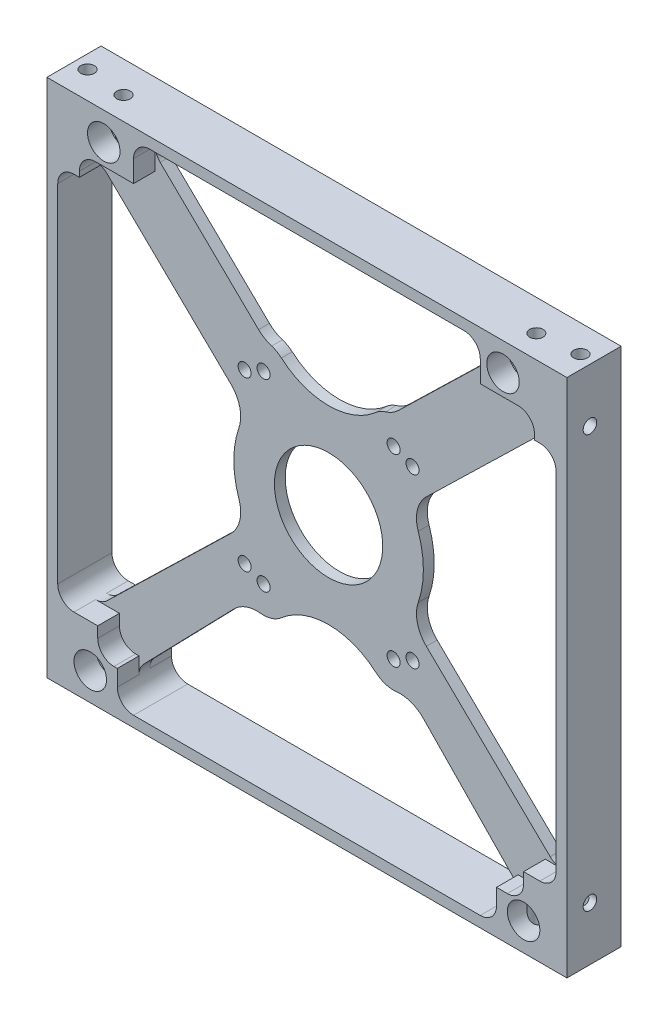
SolidWorks part; units mm, degrees
material "7075-T6 (SN)"
ref_plane "Front Plane" through (0, 0, 0) normal (0, 0, 1) x (1, 0, 0)
ref_plane "Top Plane" through (0, 0, 0) normal (0, 1, 0) x (1, 0, 0)
ref_plane "Right Plane" through (0, 0, 0) normal (1, 0, 0) x (0, 0, -1)
sketch "Sketch1" plane through (0, 0, 0) normal (0, 0, 1) x (1, 0, 0)
  line L0 (-38, 42) -> (-38, 38)
  line L1 (48, -48) -> (-48, -48)
  line L2 (48, -48) -> (48, 48)
  line L3 (48, 48) -> (-48, 48)
  line L4 (-48, -48) -> (-48, 48)
  line L5 (48, -48) -> (-48, 48) construction
  line L6 (48, 48) -> (-48, -48) construction
  line L7 (42, -42) -> (-42, -42)
  line L8 (42, -42) -> (42, 42)
  line L9 (42, 42) -> (-42, 42)
  line L10 (-42, -42) -> (-42, 42)
  line L11 (42, -42) -> (-42, 42) construction
  line L12 (42, 42) -> (-42, -42) construction
  line L13 (-38, 38) -> (-42, 38)
  line L14 (42, 38) -> (38, 38)
  line L15 (38, 38) -> (38, 42)
  line L16 (38, -42) -> (38, -38)
  line L17 (38, -38) -> (42, -38)
  line L18 (-42, -38) -> (-38, -38)
  line L19 (-38, -38) -> (-38, -42)
  point P0 (0, 0)
  point P6 (0, 0)
  point P26 (0, 0)
  dimension "D1" = 96
  dimension "D2" = 96
  dimension "D3" = 6
  dimension "D4" = 84
  dimension "D5" = 10
  dimension "D6" = 4
extrude "Boss-Extrude1" add sketch "Sketch1" along normal blind 10 contours L4 L1 L2 L3 L7 L10 L9 L8 region at (0, -46.6424, 0)
sketch "Sketch4" plane through (0, 0, 10) normal (0, 0, 1) x (1, 0, 0)
  line L0 (36.2, 42.85) -> (-37.5, 42.85) construction
  line L1 (40, -42.85) -> (-40, -42.85) construction
  line L2 (-40, -42.85) -> (-40, 42.85) construction
  line L3 (-40, 42.85) -> (-37.5, 42.85) construction
  line L4 (40, -42.85) -> (40, 42.85) construction
  line L5 (40, 42.85) -> (36.2, 42.85) construction
  line L6 (-40, 42.85) -> (40, -42.85) construction
  point P4 (0, 0)
  dimension "D1" = 73.7
  dimension "D2" = 2.5
  dimension "D3" = 85.7
  dimension "D4" = 3.8
sketch_block_instance "Block1-1"
sketch_block "Block2"
sketch "Sketch5" plane through (0, 0, 10) normal (0, 0, 1) x (1, 0, 0)
  line L0 (40.7, 38.35) -> (42, 38.35)
  line L1 (-42, 47.35) -> (-33, 47.35)
  line L2 (-42, 47.35) -> (-42, 38.35)
  line L3 (-42, 38.35) -> (-33, 38.35)
  line L4 (-33, 47.35) -> (-33, 38.35)
  line L5 (-42, 47.35) -> (-33, 38.35) construction
  line L6 (-42, 38.35) -> (-33, 47.35) construction
  line L7 (-35.5, -47.35) -> (-44.5, -47.35)
  line L8 (-35.5, -47.35) -> (-35.5, -38.35)
  line L9 (-35.5, -38.35) -> (-44.5, -38.35)
  line L10 (-44.5, -47.35) -> (-44.5, -38.35)
  line L11 (-35.5, -47.35) -> (-44.5, -38.35) construction
  line L12 (-35.5, -38.35) -> (-44.5, -47.35) construction
  line L13 (44.5, -47.35) -> (35.5, -47.35)
  line L14 (44.5, -47.35) -> (44.5, -38.35)
  line L15 (44.5, -38.35) -> (35.5, -38.35)
  line L16 (35.5, -47.35) -> (35.5, -38.35)
  line L17 (44.5, -47.35) -> (35.5, -38.35) construction
  line L18 (44.5, -38.35) -> (35.5, -47.35) construction
  line L19 (40.7, 38.35) -> (31.7, 38.35)
  line L20 (40.7, 38.35) -> (40.7, 47.35)
  line L21 (40.7, 47.35) -> (31.7, 47.35)
  line L22 (31.7, 38.35) -> (31.7, 47.35)
  line L23 (40.7, 38.35) -> (31.7, 47.35) construction
  line L24 (40.7, 47.35) -> (31.7, 38.35) construction
  line L25 (42, -42) -> (42, 42) construction
  line L26 (42, 38.35) -> (42, 42)
  line L27 (42, 42) -> (40.7, 42)
  line L28 (42, 42) -> (-42, 42) construction
  point P0 (-37.5, 42.85)
  point P1 (36.2, 42.85)
  point P3 (40, -42.85)
  point P5 (-40, -42.85)
  point P7 (-37.5, 42.85)
  point P13 (-40, -42.85)
  point P18 (40, -42.85)
  point P23 (36.2, 42.85)
  line M13 (42, -42) -> (-42, -42)
  line M14 (-42, -42) -> (-42, 42)
  line M15 (-42, 42) -> (42, 42)
  line M16 (42, 42) -> (42, -42)
  dimension "D1" = 9
  dimension "D2" = 9
  dimension "D3" = 9
  dimension "D4" = 9
  dimension "D5" = 9
  dimension "D6" = 9
  dimension "D7" = 9
  dimension "D8" = 9
extrude "Boss-Extrude2" add sketch "Sketch5" against normal up to surface (10 mm away) contours L22 L19 L20 M15 | L20 L0 M16 M15 | L4 L3 M15 M14 | L8 L9 M14 M13 | L16 L15 M13 M16 region at (41.35, 40.175, 10) region at (36.2, 40.175, 10) region at (38.75, -40.175, 10) region at (-37.5, 40.175, 10) region at (-38.75, -40.175, 10) up to face at (0, 0, 0)
fillet "Fillet1" radius 3 8 edges at (-42, 38.35, 5) (-33, 42, 5) (31.7, 42, 5) (42, 38.35, 5) (35.5, -42, 5) (42, -38.35, 5) (-35.5, -42, 5) (-42, -38.35, 5)
ref_plane "Plane1" through (0, 0, 5) normal (0, 0, -1) x (-1, 0, 0)
sketch "Sketch7" plane through (0, 0, 0) normal (0, 0, -1) x (-1, 0, 0)
  point P0 (-40, -42.85)
  point P2 (40, -42.85)
  point P4 (37.5, 42.85)
  point P6 (-36.2, 42.85)
hole_wizard "M3 Clearance Hole1" positions "3DSketch1" profile "Sketch8" hole size "M3" standard "ISO" end condition through all
sketch3d "3DSketch1"
  point P0 (36.2, 42.85, 0)
  point P3 (-37.5, 42.85, 0)
  point P6 (-40, -42.85, 0)
  point P9 (40, -42.85, 0)
sketch "Sketch8" plane through (36.2, 42.85, 0) normal (1, 0, 0) x (0, 1, 0)
  line L0 (0, 0) -> (0, 10)
  line L1 (0, 10) -> (1.7, 10)
  line L2 (1.7, 10) -> (1.7, 0)
  line L5 (1.7, 0) -> (0, 0)
  line L11 (0, -6.35) -> (0, 107.95) construction
  dimension "Thru Hole Dia." = 3.4
  dimension "Thru Hole Depth" = 10
sketch "Sketch9" plane through (0, 0, 10) normal (0, 0, 1) x (1, 0, 0)
  circle A0 centre (-37.5, 42.85) radius 3
  circle A1 centre (36.2, 42.85) radius 3
  circle A2 centre (-40, -42.85) radius 3
  circle A3 centre (40, -42.85) radius 3
  dimension "D1" = 6
  dimension "D3" = 6
  dimension "D4" = 6
  dimension "D2" = 6
extrude "Cut-Extrude1" cut sketch "Sketch9" against normal blind 4
sketch "Sketch10" plane through (0, -48, 0) normal (0, -1, 0) x (1, 0, 0)
  line L0 (48, 5) -> (32, 5) construction
  line L1 (48, 10) -> (48, 0) construction
  line L2 (-48, 5) -> (-32, 5) construction
  line L3 (-48, 10) -> (-48, 0) construction
  dimension "D1" = 16
  dimension "D2" = 16
ref_plane "Plane2" through (0, 0, 0) normal (0.7071, 0.7071, 0) x (0.7071, -0.7071, 0)
ref_plane "Plane3" through (0, 0, 0) normal (-0.7071, 0.7071, 0) x (0, 0, 1)
ref_axis "Axis1" through (0, 0, -0.5) along (0, 0, 1)
sketch "Sketch14" plane through (0, -48, 0) normal (0, -1, 0) x (1, 0, 0)
  line L0 (-48, 5) -> (-45.5, 5) construction
  line L1 (-48, 10) -> (-48, 0) construction
  line L2 (48, 5) -> (45.5, 5) construction
  line L3 (48, 10) -> (48, 0) construction
  dimension "D1" = 2.5
  dimension "D2" = 2.5
hole_wizard "M3 Tapped Hole2" positions "3DSketch3" profile "Sketch15" tap size "M3" standard "ISO"
sketch3d "3DSketch3"
  point P0 (45.5, -48, 5)
  point P3 (-45.5, -48, 5)
sketch "Sketch15" plane through (45.5, -48, 5) normal (1, 0, 0) x (0, 0, -1)
  line L0 (0, 0) -> (0, 10.2511)
  line L1 (0, 10.2511) -> (1.25, 9.5)
  line L2 (1.25, 9.5) -> (1.25, 0)
  line L5 (1.25, 0) -> (0, 0)
  line L10 (0, 10.2511) -> (-1.25, 9.5) construction
  line L11 (0, -6.35) -> (0, 107.95) construction
  dimension "Tap Drill Dia." = 2.5
  dimension "Tap Drill Depth" = 9.5
  dimension "Drill Angle" = 118
cosmetic thread "Hole Thread3" parameters "D1"=8, "D2"=3
cosmetic thread "Hole Thread4" parameters "D1"=8, "D2"=3
mirror "Mirror2" about plane through (0, 0, 0) normal (0, 1, 0) of "M3 Tapped Hole2"
sketch "Sketch19" plane through (0, 0, 0) normal (0, 0, -1) x (-1, 0, 0)
  line L12 (-32.5, -42) -> (32.5, -42)
  line L13 (-35.5, -38.35) -> (-35.5, -39)
  line L14 (-39, -38.35) -> (-35.5, -38.35)
  line L15 (-42, 35.35) -> (-42, -35.35)
  line L16 (-31.7, 38.35) -> (-39, 38.35)
  line L17 (-31.7, 39) -> (-31.7, 38.35)
  line L18 (30, 42) -> (-28.7, 42)
  line L19 (33, 38.35) -> (33, 39)
  line L20 (39, 38.35) -> (33, 38.35)
  line L21 (42, -35.35) -> (42, 35.35)
  line L22 (35.5, -38.35) -> (39, -38.35)
  line L23 (35.5, -39) -> (35.5, -38.35)
  line L24 (-32.5, -42) -> (32.5, -42)
  line L25 (-35.5, -38.35) -> (-35.5, -39)
  line L26 (-39, -38.35) -> (-35.5, -38.35)
  line L27 (-42, 35.35) -> (-42, -35.35)
  line L28 (-31.7, 38.35) -> (-39, 38.35)
  line L29 (-31.7, 39) -> (-31.7, 38.35)
  line L30 (30, 42) -> (-28.7, 42)
  line L31 (33, 38.35) -> (33, 39)
  line L32 (39, 38.35) -> (33, 38.35)
  line L33 (42, -35.35) -> (42, 35.35)
  line L34 (35.5, -38.35) -> (39, -38.35)
  line L35 (35.5, -39) -> (35.5, -38.35)
  arc A8 (-35.5, -39) -> (-32.5, -42) centre (-32.5, -39) ccw
  arc A9 (-42, -35.35) -> (-39, -38.35) centre (-39, -35.35) ccw
  arc A10 (-39, 38.35) -> (-42, 35.35) centre (-39, 35.35) ccw
  arc A11 (-28.7, 42) -> (-31.7, 39) centre (-28.7, 39) ccw
  arc A12 (33, 39) -> (30, 42) centre (30, 39) ccw
  arc A13 (42, 35.35) -> (39, 38.35) centre (39, 35.35) ccw
  arc A14 (39, -38.35) -> (42, -35.35) centre (39, -35.35) ccw
  arc A15 (32.5, -42) -> (35.5, -39) centre (32.5, -39) ccw
  arc A16 (-35.5, -39) -> (-32.5, -42) centre (-32.5, -39) ccw
  arc A17 (-42, -35.35) -> (-39, -38.35) centre (-39, -35.35) ccw
  arc A18 (-39, 38.35) -> (-42, 35.35) centre (-39, 35.35) ccw
  arc A19 (-28.7, 42) -> (-31.7, 39) centre (-28.7, 39) ccw
  arc A20 (33, 39) -> (30, 42) centre (30, 39) ccw
  arc A21 (42, 35.35) -> (39, 38.35) centre (39, 35.35) ccw
  arc A22 (39, -38.35) -> (42, -35.35) centre (39, -35.35) ccw
  arc A23 (32.5, -42) -> (35.5, -39) centre (32.5, -39) ccw
  dimension "D1" = 0
extrude "Boss-Extrude3" add sketch "Sketch19" against normal up to surface (10 mm away) up to face at (39.2, 42.85, 10)
sketch "Sketch17" plane through (-48, 0, 0) normal (-1, 0, 0) x (0, 0, 1)
  point P0 (5.752, 38.1)
  point P1 (5.752, -38.1)
sketch "Sketch18" plane through (0, 0, 0) normal (0, 0, -1) x (-1, 0, 0)
  line L0 (-48, -48) -> (-48, 48) construction
  line L1 (48, -48) -> (35, -48)
  line L2 (48, -48) -> (48, -35)
  line L3 (48, -35) -> (35, -35)
  line L4 (35, -48) -> (35, -35)
  line L6 (-35, -46) -> (-35, -48)
  line L7 (-35, -48) -> (35, -48)
  line L8 (35, -46) -> (35, -48)
  line L9 (-35, -48) -> (-48, -48)
  line L10 (-35, -48) -> (-35, -35)
  line L11 (-35, -35) -> (-48, -35)
  line L12 (-48, -48) -> (-48, -35)
  line L13 (-48, 48) -> (48, 48) construction
  line L14 (35, -46) -> (-35, -46)
  line L16 (29, 46) -> (-33.0121, 46)
  line L17 (-35, -46) -> (-35, 46)
  line L18 (48, -48) -> (48, 48) construction
  line L19 (-35, 35) -> (-32, 35)
  line L20 (-35, 35) -> (-35, 46)
  line L21 (-35, 46) -> (-32, 46)
  line L22 (-32, 35) -> (-32, 46)
  line L23 (-43, -35) -> (-35, -35)
  line L24 (-46, -32) -> (-46, 32)
  line L25 (-43, 35) -> (-35, 35)
  line L26 (-35, -35) -> (-35, 35)
  line L29 (35, 35) -> (32, 35)
  line L30 (32, 43) -> (32, 35)
  line L31 (35, 35) -> (43, 35)
  line L32 (35, 35) -> (35, -35)
  line L33 (35, -35) -> (43, -35)
  line L34 (46, 32) -> (46, -32)
  line L36 (-35, -35) -> (-40, -35)
  line L37 (-35, -35) -> (-35, -40)
  line L38 (-35, -40) -> (-37, -40)
  line L39 (-40, -35) -> (-40, -37)
  line L40 (35, -35) -> (38.6149, -35)
  line L41 (35, -35) -> (35, -40)
  line L42 (35, -40) -> (35.6149, -40)
  line L43 (38.6149, -35) -> (38.6149, -37)
  line L48 (-21.1373, 35) -> (-32, 35)
  line L49 (-21.1373, 35) -> (-21.1373, 46)
  line L50 (-21.1373, 46) -> (-29, 46)
  line L51 (-32, 35) -> (-32, 43)
  line L52 (32, 35) -> (42, 35)
  line L53 (32, 35) -> (32, 39)
  line L54 (32, 39) -> (39, 39)
  line L55 (42, 35) -> (42, 36)
  line L56 (-32, 35) -> (-42, 35)
  line L57 (-32, 35) -> (-32, 39)
  line L58 (-32, 39) -> (-39, 39)
  line L59 (-42, 35) -> (-42, 36)
  arc A0 (35.6149, -40) -> (38.6149, -37) centre (35.6149, -37) ccw
  arc A1 (-37, -40) -> (-40, -37) centre (-37, -37) cw
  arc A2 (-43, -35) -> (-46, -32) centre (-43, -32) cw
  arc A3 (-46, 32) -> (-43, 35) centre (-43, 32) cw
  arc A6 (43, 35) -> (46, 32) centre (43, 32) cw
  arc A7 (43, -35) -> (46, -32) centre (43, -32) ccw
  arc A8 (-29, 46) -> (-32, 43) centre (-29, 43) ccw
  arc A9 (29, 46) -> (32, 43) centre (29, 43) cw
  arc A10 (39, 39) -> (42, 36) centre (39, 36) cw
  arc A11 (-39, 39) -> (-42, 36) centre (-39, 36) ccw
  point P39 (38.6149, -40)
  point P44 (-46, -35)
  point P57 (46, -35)
  dimension "D15" = 3
  dimension "D16" = 3
  dimension "D17" = 3
  dimension "D22" = 3
  dimension "D1" = 13
  dimension "D2" = 13
  dimension "D4" = 13
  dimension "D5" = 13
  dimension "D3" = 2
  dimension "D6" = 2
  dimension "D7" = 3
  dimension "D8" = 13
  dimension "D9" = 2
  dimension "D11" = 2
  dimension "D12" = 8
  dimension "D13" = 8
  dimension "D14" = 3.6149
  dimension "D10" = 3
  dimension "D18" = 6
  dimension "D19" = 9
  dimension "D20" = 9
  dimension "D21" = 6
extrude "Cut-Extrude2" cut sketch "Sketch18" against normal blind 10 contours A9 L16 L49 L48 L19 L17 L10 L14 L4 L32 L29 L30 | L16 A8 L22 L48 L49 | L3 A7 L34 A6 L31 L32 L33 | A3 L24 A2 L23 L11 L17 L25 | L42 A0 L43 L33 L4 | A1 L38 L17 L11 L39 | L53 L52 L55 A10 L54 | L57 L56 L59 A11 L58 region at (-0.4981, -1.2155, 0) region at (-40.4756, 0, 0) region at (-36.6714, -37.2811, 0) region at (37.3468, -37.3468, 0) region at (40.4756, 0, 0) region at (26.4904, 40.4206, 0)
fillet "Fillet2" radius 3 2 edges at (35, -46, 5) (-35, -46, 5)
hole_wizard "M3 Tapped Hole3" positions "3DSketch4" profile "Sketch20" tap size "M3" standard "ISO"
sketch3d "3DSketch4"
  point P0 (-48, 38.1, 5.752)
  point P3 (-48, -38.1, 5.752)
sketch "Sketch20" plane through (-48, 38.1, 5.752) normal (0, 1, 0) x (0, 0, 1)
  line L0 (0, 0) -> (0, 8.2511)
  line L1 (0, 8.2511) -> (1.25, 7.5)
  line L2 (1.25, 7.5) -> (1.25, 0)
  line L5 (1.25, 0) -> (0, 0)
  line L10 (0, 8.2511) -> (-1.25, 7.5) construction
  line L11 (0, -6.35) -> (0, 107.95) construction
  dimension "Tap Drill Dia." = 2.5
  dimension "Tap Drill Depth" = 7.5
  dimension "Drill Angle" = 118
cosmetic thread "Hole Thread9" parameters "D1"=3.0702, "D2"=3
cosmetic thread "Hole Thread10" parameters "D1"=3.0702, "D2"=3
pattern_circular "CirPattern1" count 4 every 90 about axis through (0, 0, -0.5) along (0, 0, 1) of "M3 Tapped Hole3"
sketch "Sketch21" plane through (0, 0, 5) normal (0, 0, -1) x (-1, 0, 0)
  line L20 (46, -32) -> (46, 32)
  line L21 (38.6149, -35) -> (43, -35)
  line L22 (38.6149, -37) -> (38.6149, -35)
  line L23 (35, -40) -> (35.6149, -40)
  line L24 (35, -43) -> (35, -40)
  line L25 (-32, -46) -> (32, -46)
  line L26 (-35, -40) -> (-35, -43)
  line L27 (-37, -40) -> (-35, -40)
  line L28 (-40, -35) -> (-40, -37)
  line L29 (-43, -35) -> (-40, -35)
  line L30 (-46, 32) -> (-46, -32)
  line L31 (-42, 35) -> (-43, 35)
  line L32 (-42, 36) -> (-42, 35)
  line L33 (-32, 39) -> (-39, 39)
  line L34 (-32, 43) -> (-32, 39)
  line L35 (29, 46) -> (-29, 46)
  line L36 (32, 39) -> (32, 43)
  line L37 (39, 39) -> (32, 39)
  line L38 (42, 35) -> (42, 36)
  line L39 (43, 35) -> (42, 35)
  line L40 (46, -32) -> (46, 32)
  line L41 (38.6149, -35) -> (43, -35)
  line L42 (38.6149, -37) -> (38.6149, -35)
  line L43 (35, -40) -> (35.6149, -40)
  line L44 (35, -43) -> (35, -40)
  line L45 (-32, -46) -> (32, -46)
  line L46 (-35, -40) -> (-35, -43)
  line L47 (-37, -40) -> (-35, -40)
  line L48 (-40, -35) -> (-40, -37)
  line L49 (-43, -35) -> (-40, -35)
  line L50 (-46, 32) -> (-46, -32)
  line L51 (-42, 35) -> (-43, 35)
  line L52 (-42, 36) -> (-42, 35)
  line L53 (-32, 39) -> (-39, 39)
  line L54 (-32, 43) -> (-32, 39)
  line L55 (29, 46) -> (-29, 46)
  line L56 (32, 39) -> (32, 43)
  line L57 (39, 39) -> (32, 39)
  line L58 (42, 35) -> (42, 36)
  line L59 (43, 35) -> (42, 35)
  arc A12 (46, 32) -> (43, 35) centre (43, 32) ccw
  arc A13 (43, -35) -> (46, -32) centre (43, -32) ccw
  arc A14 (35.6149, -40) -> (38.6149, -37) centre (35.6149, -37) ccw
  arc A15 (32, -46) -> (35, -43) centre (32, -43) ccw
  arc A16 (-35, -43) -> (-32, -46) centre (-32, -43) ccw
  arc A17 (-40, -37) -> (-37, -40) centre (-37, -37) ccw
  arc A18 (-46, -32) -> (-43, -35) centre (-43, -32) ccw
  arc A19 (-43, 35) -> (-46, 32) centre (-43, 32) ccw
  arc A20 (-39, 39) -> (-42, 36) centre (-39, 36) ccw
  arc A21 (-29, 46) -> (-32, 43) centre (-29, 43) ccw
  arc A22 (32, 43) -> (29, 46) centre (29, 43) ccw
  arc A23 (42, 36) -> (39, 39) centre (39, 36) ccw
  arc A24 (46, 32) -> (43, 35) centre (43, 32) ccw
  arc A25 (43, -35) -> (46, -32) centre (43, -32) ccw
  arc A26 (35.6149, -40) -> (38.6149, -37) centre (35.6149, -37) ccw
  arc A27 (32, -46) -> (35, -43) centre (32, -43) ccw
  arc A28 (-35, -43) -> (-32, -46) centre (-32, -43) ccw
  arc A29 (-40, -37) -> (-37, -40) centre (-37, -37) ccw
  arc A30 (-46, -32) -> (-43, -35) centre (-43, -32) ccw
  arc A31 (-43, 35) -> (-46, 32) centre (-43, 32) ccw
  arc A32 (-39, 39) -> (-42, 36) centre (-39, 36) ccw
  arc A33 (-29, 46) -> (-32, 43) centre (-29, 43) ccw
  arc A34 (32, 43) -> (29, 46) centre (29, 43) ccw
  arc A35 (42, 36) -> (39, 39) centre (39, 36) ccw
  dimension "D1" = 0
extrude "Boss-Extrude4" add sketch "Sketch21" along normal blind 1 and the other way blind 1
sketch "Sketch22" plane through (0, 0, 4) normal (0, 0, -1) x (-1, 0, 0)
  line L0 (-8.9993, -15.0087) -> (-34.1522, -40.91)
  line L1 (-32, -46) -> (32, -46)
  line L2 (34.1522, -40.91) -> (8.9993, -15.0087)
  line L3 (0, 0) -> (-29.2584, -30.1289) construction
  line L4 (0, -46) -> (0, 0) construction
  line L5 (-8.9993, -15.0087) -> (8.9993, -15.0087) construction
  line L6 (-48, -48) -> (48, -48) construction
  circle A0 centre (0, 0) radius 10
  circle A1 centre (0, 0) radius 17.5
  arc A2 (-34.1522, -40.91) -> (-32, -46) centre (-32, -43) ccw
  arc A3 (32, -46) -> (34.1522, -40.91) centre (32, -43) ccw
  arc A9 (-35, -43) -> (-32, -46) centre (-32, -43) ccw construction
  dimension "D1" = 20
  dimension "D2" = 35
  dimension "D5" = 3
  dimension "D3" = 4
  dimension "D4" = 2
extrude "Cut-Extrude3" cut sketch "Sketch22" against normal blind 11 and the other way blind 1 contours L1 A3 L2 A1 L0 A2 | A0 region at (0, -33.9469, 4) region at (0, 0, 4)
fillet "Fillet3" radius 6 2 edges at (-8.9993, -15.0087, 5) (8.9993, -15.0087, 5)
pattern_circular "CirPattern2" count 2 every 90 about axis through (0, 0, -0.5) along (0, 0, 1) of "Cut-Extrude3", "Fillet3" other way count 2
sketch "Sketch23" plane through (0, 0, 4) normal (0, 0, -1) x (-1, 0, 0)
  line L0 (29, 46) -> (-29, 46)
  line L1 (31.09, 40.8478) -> (7.6401, 18.0755)
  line L2 (18.0429, 11.9458) -> (40.91, 34.1522) construction
  line L3 (-7.6401, 18.0755) -> (-31.09, 40.8478)
  line L4 (-40.91, 34.1522) -> (-18.0429, 11.9458) construction
  circle A0 centre (-29, 43) radius 3
  circle A1 centre (29, 43) radius 3
  arc A7 (32, 43) -> (29, 46) centre (29, 43) ccw construction
  arc A8 (-29, 46) -> (-32, 43) centre (-29, 43) ccw construction
  arc A9 (3.9504, 17.0483) -> (-3.9504, 17.0483) centre (0, 0) ccw
  arc A10 (7.6401, 18.0755) -> (3.9504, 17.0483) centre (4.8534, 20.945) cw
  arc A11 (-3.9504, 17.0483) -> (-7.6401, 18.0755) centre (-4.8534, 20.945) cw
  arc M40 (32, 43) -> (29, 46) centre (29, 43) ccw
  line M41 (29, 46) -> (-29, 46)
  arc M42 (-29, 46) -> (-32, 43) centre (-29, 43) ccw
  dimension "D1" = 6
  dimension "D2" = 6
  dimension "D3" = 17.5
  dimension "D4" = 4
extrude "Cut-Extrude4" cut sketch "Sketch23" against normal blind 10 contours A11 A9 A10 L1 A1 A0 L3 M41 | A1 M40 | A0 M42 region at (0, 34.3208, 4) region at (-29, 43, 4) region at (29, 43, 4)
sketch "Sketch24" plane through (0, 0, 4) normal (0, 0, -1) x (-1, 0, 0)
  line L0 (11.9458, -18.0429) -> (34.1522, -40.91) construction
  line L1 (-15.5, 15.5) -> (15.5, 15.5) construction
  line L2 (-15.5, 15.5) -> (-15.5, -15.5) construction
  line L3 (-15.5, -15.5) -> (15.5, -15.5) construction
  line L4 (15.5, 15.5) -> (15.5, -15.5) construction
  line L5 (-15.5, 15.5) -> (15.5, -15.5) construction
  line L6 (-15.5, -15.5) -> (15.5, 15.5) construction
  line L7 (-12, 17) -> (12, 17) construction
  line L8 (-12, 17) -> (-12, -17) construction
  line L9 (-12, -17) -> (12, -17) construction
  line L10 (12, 17) -> (12, -17) construction
  line L11 (-12, 17) -> (12, -17) construction
  line L12 (-12, -17) -> (12, 17) construction
  line L13 (-34.1522, -40.91) -> (-11.9458, -18.0429) construction
  line L37 (-32, 43) -> (-32, 39)
  line L38 (-32, 39) -> (-39, 39)
  line L39 (-42, 36) -> (-42, 35)
  line L40 (-42, 35) -> (-43, 35)
  line L41 (-40.91, 34.1522) -> (-18.0429, 11.9458)
  line L42 (-18.0429, -11.9458) -> (-40.91, -34.1522)
  line L43 (-43, -35) -> (-40, -35)
  line L44 (-40, -35) -> (-40, -37)
  line L45 (-37, -40) -> (-35, -40)
  line L46 (-35, -40) -> (-35, -43)
  line L47 (-34.1522, -40.91) -> (-11.9458, -18.0429)
  line L48 (11.9458, -18.0429) -> (34.1522, -40.91)
  line L49 (35, -43) -> (35, -40)
  line L50 (35, -40) -> (35.6149, -40)
  line L51 (38.6149, -37) -> (38.6149, -35)
  line L52 (38.6149, -35) -> (43, -35)
  line L53 (40.91, -34.1522) -> (18.0429, -11.9458)
  line L54 (18.0429, 11.9458) -> (40.91, 34.1522)
  line L55 (43, 35) -> (42, 35)
  line L56 (42, 35) -> (42, 36)
  line L57 (39, 39) -> (32, 39)
  line L58 (32, 39) -> (32, 43)
  line L59 (31.09, 40.8478) -> (7.6401, 18.0755)
  line L60 (-7.6401, 18.0755) -> (-31.09, 40.8478)
  line L61 (-32, 43) -> (-32, 39)
  line L62 (-32, 39) -> (-39, 39)
  line L63 (-42, 36) -> (-42, 35)
  line L64 (-42, 35) -> (-43, 35)
  line L65 (-40.91, 34.1522) -> (-18.0429, 11.9458)
  line L66 (-18.0429, -11.9458) -> (-40.91, -34.1522)
  line L67 (-43, -35) -> (-40, -35)
  line L68 (-40, -35) -> (-40, -37)
  line L69 (-37, -40) -> (-35, -40)
  line L70 (-35, -40) -> (-35, -43)
  line L73 (35, -43) -> (35, -40)
  line L74 (35, -40) -> (35.6149, -40)
  line L75 (38.6149, -37) -> (38.6149, -35)
  line L76 (38.6149, -35) -> (43, -35)
  line L77 (40.91, -34.1522) -> (18.0429, -11.9458)
  line L78 (18.0429, 11.9458) -> (40.91, 34.1522)
  line L79 (43, 35) -> (42, 35)
  line L80 (42, 35) -> (42, 36)
  line L81 (39, 39) -> (32, 39)
  line L82 (32, 39) -> (32, 43)
  line L83 (31.09, 40.8478) -> (7.6401, 18.0755)
  line L84 (-7.6401, 18.0755) -> (-31.09, 40.8478)
  arc A5 (14.8932, -21.0779) -> (7.0563, -16.2515) centre (12, -17) cw
  arc A6 (11.9458, -18.0429) -> (5.6905, -16.549) centre (7.6415, -22.2229) ccw construction
  arc A7 (-7.1022, -15.994) -> (-14.8932, -21.0779) centre (-12, -17) cw
  arc A8 (-5.6905, -16.549) -> (5.6905, -16.549) centre (0, 0) ccw construction
  arc A9 (-8.7123, -20.7671) -> (8.7123, -20.7671) centre (0, -30.75) cw
  arc A10 (-5.6905, -16.549) -> (5.6905, -16.549) centre (0, 0) ccw
  arc A29 (-32, 43) -> (-31.09, 40.8478) centre (-29, 43) ccw
  arc A30 (-39, 39) -> (-42, 36) centre (-39, 36) ccw
  arc A31 (-40.91, 34.1522) -> (-43, 35) centre (-43, 32) ccw
  arc A32 (-16.549, 5.6905) -> (-18.0429, 11.9458) centre (-22.2229, 7.6415) ccw
  arc A33 (-16.549, 5.6905) -> (-16.549, -5.6905) centre (0, 0) ccw
  arc A34 (-18.0429, -11.9458) -> (-16.549, -5.6905) centre (-22.2229, -7.6415) ccw
  arc A35 (-43, -35) -> (-40.91, -34.1522) centre (-43, -32) ccw
  arc A36 (-40, -37) -> (-37, -40) centre (-37, -37) ccw
  arc A37 (-34.1522, -40.91) -> (-35, -43) centre (-32, -43) ccw
  arc A38 (-5.6905, -16.549) -> (-11.9458, -18.0429) centre (-7.6415, -22.2229) ccw
  arc A39 (-5.6905, -16.549) -> (5.6905, -16.549) centre (0, 0) ccw
  arc A40 (11.9458, -18.0429) -> (5.6905, -16.549) centre (7.6415, -22.2229) ccw
  arc A41 (35, -43) -> (34.1522, -40.91) centre (32, -43) ccw
  arc A42 (35.6149, -40) -> (38.6149, -37) centre (35.6149, -37) ccw
  arc A43 (40.91, -34.1522) -> (43, -35) centre (43, -32) ccw
  arc A44 (16.549, -5.6905) -> (18.0429, -11.9458) centre (22.2229, -7.6415) ccw
  arc A45 (16.549, -5.6905) -> (16.549, 5.6905) centre (0, 0) ccw
  arc A46 (18.0429, 11.9458) -> (16.549, 5.6905) centre (22.2229, 7.6415) ccw
  arc A47 (43, 35) -> (40.91, 34.1522) centre (43, 32) ccw
  arc A48 (42, 36) -> (39, 39) centre (39, 36) ccw
  arc A49 (31.09, 40.8478) -> (32, 43) centre (29, 43) ccw
  arc A50 (3.9504, 17.0483) -> (7.6401, 18.0755) centre (4.8534, 20.945) ccw
  arc A51 (3.9504, 17.0483) -> (-3.9504, 17.0483) centre (0, 0) ccw
  arc A52 (-7.6401, 18.0755) -> (-3.9504, 17.0483) centre (-4.8534, 20.945) ccw
  arc A53 (-32, 43) -> (-31.09, 40.8478) centre (-29, 43) ccw
  arc A54 (-39, 39) -> (-42, 36) centre (-39, 36) ccw
  arc A55 (-40.91, 34.1522) -> (-43, 35) centre (-43, 32) ccw
  arc A56 (-16.549, 5.6905) -> (-18.0429, 11.9458) centre (-22.2229, 7.6415) ccw
  arc A57 (-16.549, 5.6905) -> (-16.549, -5.6905) centre (0, 0) ccw
  arc A58 (-18.0429, -11.9458) -> (-16.549, -5.6905) centre (-22.2229, -7.6415) ccw
  arc A59 (-43, -35) -> (-40.91, -34.1522) centre (-43, -32) ccw
  arc A60 (-40, -37) -> (-37, -40) centre (-37, -37) ccw
  arc A61 (-34.1522, -40.91) -> (-35, -43) centre (-32, -43) ccw
  arc A65 (35, -43) -> (34.1522, -40.91) centre (32, -43) ccw
  arc A66 (35.6149, -40) -> (38.6149, -37) centre (35.6149, -37) ccw
  arc A67 (40.91, -34.1522) -> (43, -35) centre (43, -32) ccw
  arc A68 (16.549, -5.6905) -> (18.0429, -11.9458) centre (22.2229, -7.6415) ccw
  arc A69 (16.549, -5.6905) -> (16.549, 5.6905) centre (0, 0) ccw
  arc A70 (18.0429, 11.9458) -> (16.549, 5.6905) centre (22.2229, 7.6415) ccw
  arc A71 (43, 35) -> (40.91, 34.1522) centre (43, 32) ccw
  arc A72 (42, 36) -> (39, 39) centre (39, 36) ccw
  arc A73 (31.09, 40.8478) -> (32, 43) centre (29, 43) ccw
  arc A74 (3.9504, 17.0483) -> (7.6401, 18.0755) centre (4.8534, 20.945) ccw
  arc A75 (3.9504, 17.0483) -> (-3.9504, 17.0483) centre (0, 0) ccw
  arc A76 (-7.6401, 18.0755) -> (-3.9504, 17.0483) centre (-4.8534, 20.945) ccw
  point P0 (0, 0)
  point P6 (0, 0)
  line M24 (-34.1522, -40.91) -> (-11.9458, -18.0429)
  arc M25 (-11.9458, -18.0429) -> (-5.6905, -16.549) centre (-7.6415, -22.2229) cw
  arc M26 (-5.6905, -16.549) -> (5.6905, -16.549) centre (0, 0) ccw
  arc M27 (5.6905, -16.549) -> (11.9458, -18.0429) centre (7.6415, -22.2229) cw
  line M28 (11.9458, -18.0429) -> (34.1522, -40.91)
  dimension "D5" = 5
  dimension "D6" = 5
  dimension "D1" = 31
  dimension "D2" = 31
  dimension "D3" = 24
  dimension "D4" = 34
hole_wizard "M2 Clearance Hole1" positions "3DSketch5" profile "Sketch25" hole size "M2" standard "ISO"
sketch3d "3DSketch5"
  point P0 (-15.5, -15.5, 4)
  point P3 (15.5, -15.5, 4)
  point P6 (15.5, 15.5, 4)
  point P9 (-15.5, 15.5, 4)
sketch "Sketch25" plane through (-15.5, -15.5, 4) normal (1, 0, 0) x (0, 1, 0)
  line L0 (0, 0) -> (0, 8.221)
  line L1 (0, 8.221) -> (1.2, 7.5)
  line L2 (1.2, 7.5) -> (1.2, 0)
  line L5 (1.2, 0) -> (0, 0)
  line L10 (0, 8.221) -> (-1.2, 7.5) construction
  line L11 (0, -6.35) -> (0, 107.95) construction
  dimension "Hole Dia." = 2.4
  dimension "Hole Depth" = 7.5
  dimension "Drill Angle" = 118
extrude "Boss-Extrude6" add sketch "Sketch24" against normal up to surface (2 mm away) contours A5 M28 M27 | A7 M25 M24 | A7 A9 M26 M25 | A9 A5 M26 M27 region at (10.4328, -19.2931, 4) region at (5.4616, -17.8182, 4) region at (-5.4616, -17.8182, 4) region at (-10.4328, -19.2931, 4) up to face at (-16.7, -15.5, 6)
fillet "Fillet5" radius 6 2 edges at (-14.8932, -21.0779, 5) (14.8932, -21.0779, 5)
pattern_circular "CirPattern8" count 2 every 180 about axis through (0, 0, -0.5) along (0, 0, 1) of "Boss-Extrude6"
fillet "Fillet6" radius 6 2 edges at (-11.6702, 21.9891, 5) (11.6702, 21.9891, 5)
hole_wizard "M2 Clearance Hole2" positions "3DSketch6" profile "Sketch27" hole size "M2" standard "ISO"
sketch3d "3DSketch6"
  point P0 (-12, -17, 4)
  point P3 (12, -17, 4)
  point P6 (12, 17, 4)
  point P9 (-12, 17, 4)
sketch "Sketch27" plane through (-12, -17, 4) normal (1, 0, 0) x (0, 1, 0)
  line L0 (0, 0) -> (0, 8.221)
  line L1 (0, 8.221) -> (1.2, 7.5)
  line L2 (1.2, 7.5) -> (1.2, 0)
  line L5 (1.2, 0) -> (0, 0)
  line L10 (0, 8.221) -> (-1.2, 7.5) construction
  line L11 (0, -6.35) -> (0, 107.95) construction
  dimension "Hole Dia." = 2.4
  dimension "Hole Depth" = 7.5
  dimension "Drill Angle" = 118
equation "\"D2@Sketch5\"=\"D1@Sketch5\""
equation "\"D4@Sketch5\"=\"D3@Sketch5\""
equation "\"D5@Sketch5\"=\"D3@Sketch5\""
equation "\"D6@Sketch5\"=\"D3@Sketch5\""
equation "\"D8@Sketch5\"=\"D7@Sketch5\""
equation "\"D3@Sketch9\"=\"D1@Sketch9\""
equation "\"D4@Sketch9\"=\"D1@Sketch9\""
equation "\"D2@Sketch9\"=\"D3@Sketch9\""
equation "\"D2@Sketch10\"=\"D1@Sketch10\""
equation "\"D2@Sketch14\"=\"D1@Sketch14\""
equation "\"D4@Sketch18\"=\"D1@Sketch18\""
equation "\"D2@Sketch18\"=\"D1@Sketch18\""
equation "\"D5@Sketch18\"=\"D1@Sketch18\""
equation "\"D6@Sketch18\"=\"D3@Sketch18\""
equation "\"D9@Sketch18\"=\"D3@Sketch18\""
equation "\"D13@Sketch18\"=\"D12@Sketch18\""
equation "\"D21@Sketch18\"=\"D18@Sketch18\""
equation "\"D20@Sketch18\"=\"D19@Sketch18\""
equation "\"D2@Sketch23\"=\"D1@Sketch23\""
equation "\"D2@Sketch24\"=\"D1@Sketch24\""
